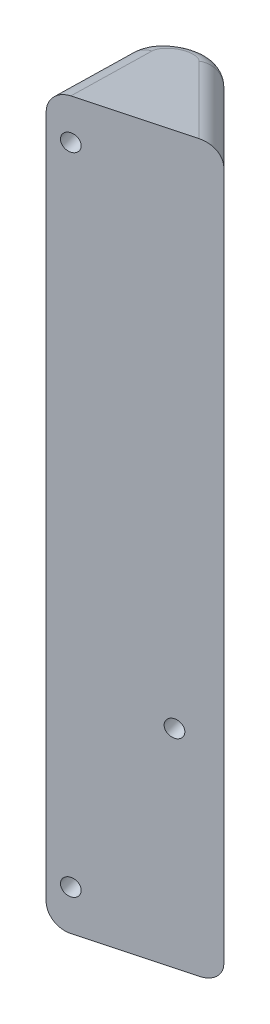
SolidWorks part; units mm, degrees
ref_plane "Front Plane" through (0, 0, 0) normal (1, 0, 0) x (0, 1, 0)
ref_plane "Top Plane" through (0, 0, 0) normal (0, 0, 1) x (0, 1, 0)
ref_plane "Right Plane" through (0, 0, 0) normal (0, 1, 0) x (-1, 0, 0)
sketch "Sketch1" plane through (0, 0, 0) normal (0, 1, 0) x (-1, 0, 0)
  line L0 (75.9973, -4.6664) -> (58.6106, -9.3251)
  line L1 (73.0995, -5.4428) -> (9.3484, -22.5249) construction
  line L2 (5.2259, -23.5943) -> (95.9286, -23.5943) construction
  line L3 (58.6106, -9.3251) -> (71.6106, -22.3251)
  line L4 (75.9973, -4.6664) -> (79.5073, -17.766)
  line L6 (75.341, 5.5105) -> (77.6703, -3.1828) construction
  arc A0 (4.26, -22.8531) -> (5.4847, -23.5602) centre (5.2259, -22.5943) ccw construction
  arc A3 (71.6106, -22.3251) -> (79.5073, -17.766) centre (74.9482, -18.9876) ccw
  point P2 (74.5073, -19.7667)
  dimension "D1" = 18
  dimension "D2" = 13
  dimension "D3" = 2
  dimension "D4" = 90
  dimension "D5" = 60
extrude "Boss-Extrude1" add sketch "Sketch1" along normal mid plane 90
sketch "Sketch2" plane through (-69.7398, 0, 18.6867) normal (-0.9659, 0, 0.2588) x (0, -1, 0)
  line L0 (-45, -24.1769) -> (-40, -42.4586)
  line L2 (-40, -42.4586) -> (-45, -42.4586)
  line L3 (-45, -42.4586) -> (-45, -24.1769)
  line L4 (0, -24.1769) -> (0, -24.8554) construction
  line L5 (-45, -24.1769) -> (45, -24.1769) construction
  line L6 (45, -42.4586) -> (45, -24.1769)
  line L7 (40, -42.4586) -> (45, -42.4586)
  line L8 (45, -24.1769) -> (40, -42.4586)
  line L9 (-45, -42.4586) -> (45, -42.4586) construction
  point P3 (-40, -20.5793)
  point P15 (-40, -6.9686)
  dimension "D1" = 5
extrude "Cut-Extrude1" cut sketch "Sketch2" against normal through all
fillet "Fillet1" radius 2.5 6 edges at (-77.7523, -43.1455, -11.2162) (-77.7523, 43.1455, -11.2162) (-65.1106, -42.8227, -15.8251) (-65.1106, 42.8227, -15.8251) (-77.3082, -40.044, -23.0752) (-77.3082, 40.044, -23.0752)
sketch "Sketch3" plane through (-6.2575, 0, -23.3531) normal (0.2588, 0, 0.9659) x (0.9659, 0, -0.2588)
  line L0 (-56.706, 45) -> (-69.7, 45) construction
  line L1 (-72.2, 42.4082) -> (-72.2, -42.4082) construction
  line L2 (-69.7, -45) -> (-56.706, -45) construction
  line L3 (-48.1, -14.25) -> (-61.1, -14.25) construction
  line L4 (-54.2, 42.7501) -> (-54.2, -42.7501) construction
  circle A0 centre (-69.7, 40) radius 1.05
  circle A1 centre (-69.7, -40) radius 1.05
  circle A2 centre (-59.2, -19.25) radius 1.05
  dimension "D1" = 2.1
  dimension "D2" = 5
  dimension "D6" = 5
  dimension "D3" = 2.5
  dimension "D4" = 2.5
  dimension "D5" = 5
  dimension "D7" = 5
extrude "Cut-Extrude2" cut sketch "Sketch3" against normal blind 5
